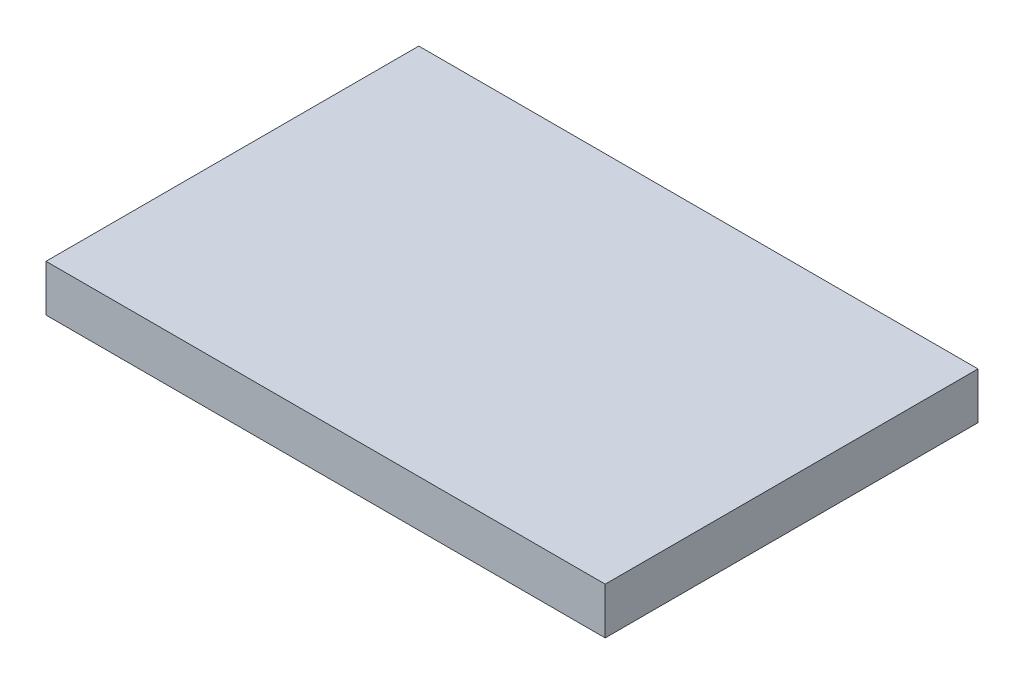
SolidWorks part; units mm, degrees
ref_plane "Front Plane" through (0, 0, 0) normal (0, 0, 1) x (1, 0, 0)
ref_plane "Top Plane" through (0, 0, 0) normal (0, 1, 0) x (1, 0, 0)
ref_plane "Right Plane" through (0, 0, 0) normal (1, 0, 0) x (0, 0, -1)
sketch "Sketch1" plane through (0, 4470, 0) normal (0, -1, 0) x (1, 0, 0)
  line L1 (-86.4895, 26.9213) -> (33.5105, 26.9213)
  line L2 (-86.4895, 26.9213) -> (-86.4895, -53.0787)
  line L3 (-86.4895, -53.0787) -> (33.5105, -53.0787)
  line L4 (33.5105, 26.9213) -> (33.5105, -53.0787)
  dimension "D1" = 80
  dimension "D2" = 120
extrude "Boss-Extrude1" add sketch "Sketch1" along normal blind 10
